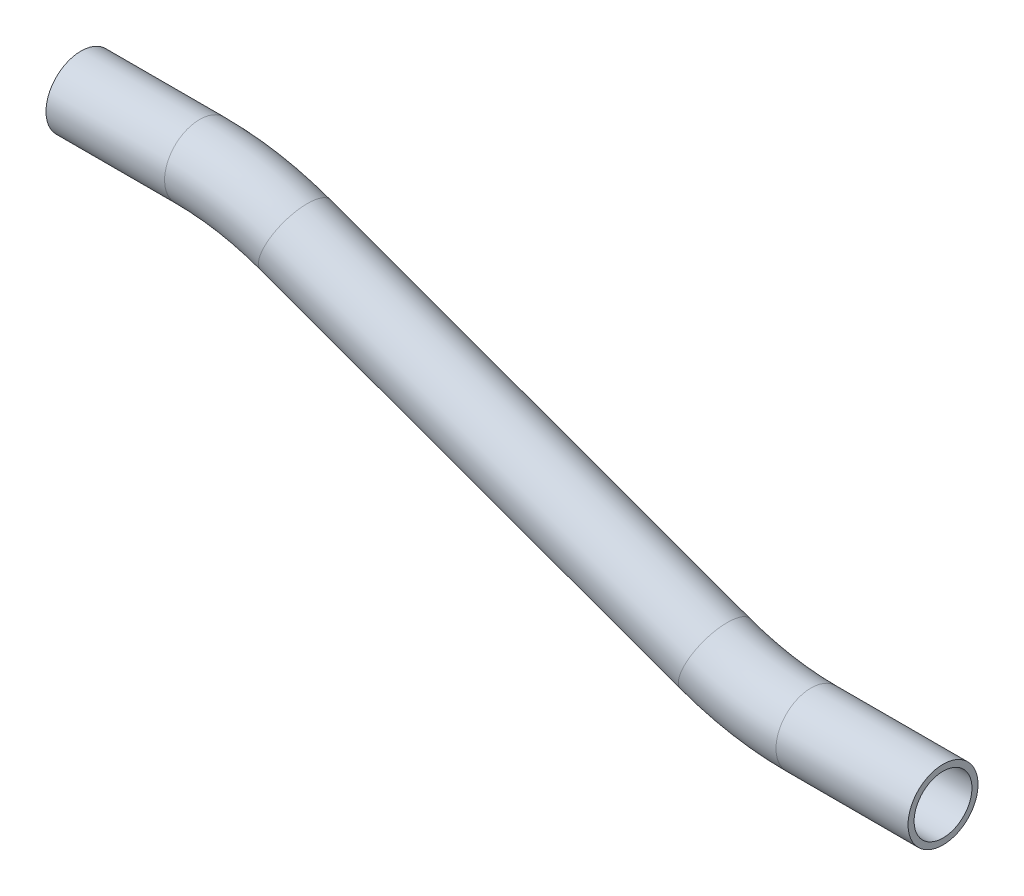
SolidWorks part; units mm, degrees
material "6061 Alloy"
ref_plane "Front Plane" through (0, 0, 0) normal (0, 0, 1) x (1, 0, 0)
ref_plane "Top Plane" through (0, 0, 0) normal (0, 1, 0) x (1, 0, 0)
ref_plane "Right Plane" through (0, 0, 0) normal (1, 0, 0) x (0, 0, -1)
sketch "Sketch1" plane through (0, 0, 0) normal (0, 0, 1) x (1, 0, 0)
  line L0 (29.8322, -12.2) -> (62.1161, -12.2)
  line L1 (88.178, -16.7954) -> (202.4982, -58.4045)
  line L2 (228.5602, -63) -> (264.5016, -63)
  line L3 (228.5602, -63) -> (76.0924, -63) construction
  line L4 (88.178, -16.7954) -> (202.4982, -58.4045) construction
  line L5 (202.4982, -58.4045) -> (282.0836, -87.3713) construction
  line L6 (202.4982, -58.4045) -> (88.178, -16.7954) construction
  line L7 (88.178, -16.7954) -> (-104.6523, 53.3891) construction
  line L8 (29.8322, -12.2) -> (62.1161, -12.2) construction
  line L9 (62.1161, -12.2) -> (185.9661, -12.2) construction
  arc A0 (62.1161, -12.2) -> (88.178, -16.7954) centre (62.1161, -88.4) cw
  arc A1 (202.4982, -58.4045) -> (228.5602, -63) centre (228.5602, 13.2) ccw
  point P9 (75.5522, -12.2)
  point P14 (215.124, -63)
  point P15 (0, 0)
  dimension "D1" = 76.2
  dimension "D2" = 76.2
  dimension "D4" = 20
  dimension "D3" = 20
  dimension "D5" = 148.5293
  dimension "D6" = 45.72
  dimension "D7" = 49.3776
ref_plane "Plane1" through (29.8322, -12.2, 0) normal (1, 0, 0) x (0, 0, -1)
sketch "Sketch2" plane through (29.8322, -12.2, 0) normal (1, 0, 0) x (0, 0, -1)
  circle A0 centre (0, 0) radius 9.525
  circle A1 centre (0, 0) radius 7.874
  dimension "D1" = 15.748
  dimension "D2" = 19.05
sweep "Sweep1" add profiles "Sketch2" path "Sketch1"
